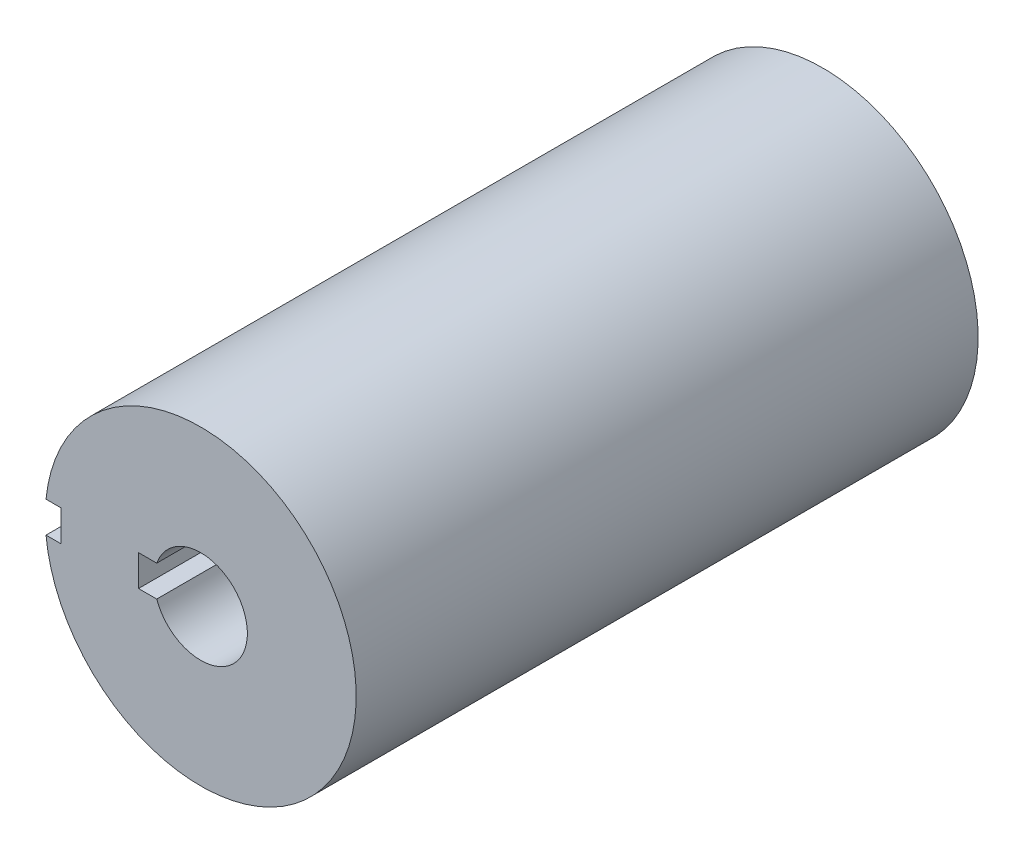
SolidWorks part; units mm, degrees
ref_plane "Front Plane" through (0, 0, 0) normal (0, 0, 1) x (1, 0, 0)
ref_plane "Top Plane" through (0, 0, 0) normal (0, 1, 0) x (1, 0, 0)
ref_plane "Right Plane" through (0, 0, 0) normal (1, 0, 0) x (0, 0, -1)
sketch "Sketch5" plane through (0, 0, 0) normal (0, 0, 1) x (1, 0, 0)
  circle A0 centre (0, 0) radius 5
  circle A1 centre (0, 0) radius 1.5
  dimension "D1" = 10
  dimension "D2" = 3
extrude "Boss-Extrude2" add sketch "Sketch5" along normal blind 12
sketch "Sketch6" plane through (0, 0, 12) normal (0, 0, 1) x (1, 0, 0)
  line L1 (-2, 0.5) -> (-1, 0.5)
  line L2 (-2, 0.5) -> (-2, -0.5)
  line L3 (-2, -0.5) -> (-1, -0.5)
  line L4 (-1, 0.5) -> (-1, -0.5)
  line L5 (-2, 0.5) -> (-1, -0.5) construction
  line L6 (-2, -0.5) -> (-1, 0.5) construction
  circle A0 centre (0, 0) radius 1.5 construction
  point P0 (-1.5, 0)
  dimension "D1" = 1
  dimension "D2" = 1
extrude "Cut-Extrude4" cut sketch "Sketch6" against normal blind 12
sketch "Sketch7" plane through (0, 0, 12) normal (0, 0, 1) x (1, 0, 0)
  line L1 (-5.5, 0.5) -> (-4.5, 0.5)
  line L2 (-5.5, 0.5) -> (-5.5, -0.5)
  line L3 (-5.5, -0.5) -> (-4.5, -0.5)
  line L4 (-4.5, 0.5) -> (-4.5, -0.5)
  line L5 (-5.5, 0.5) -> (-4.5, -0.5) construction
  line L6 (-5.5, -0.5) -> (-4.5, 0.5) construction
  circle A0 centre (0, 0) radius 5 construction
  point P0 (-5, 0)
  dimension "D1" = 1
  dimension "D2" = 1
extrude "Cut-Extrude6" cut sketch "Sketch7" against normal blind 4
sketch "Sketch8" plane through (0, 0, 0) normal (0, 0, -1) x (-1, 0, 0)
  line L1 (4.5, 0.5) -> (5.5, 0.5)
  line L2 (4.5, 0.5) -> (4.5, -0.5)
  line L3 (4.5, -0.5) -> (5.5, -0.5)
  line L4 (5.5, 0.5) -> (5.5, -0.5)
  line L5 (4.5, 0.5) -> (5.5, -0.5) construction
  line L6 (4.5, -0.5) -> (5.5, 0.5) construction
  circle A0 centre (0, 0) radius 5 construction
  point P0 (5, 0)
  dimension "D1" = 1
  dimension "D2" = 1
extrude "Cut-Extrude7" cut sketch "Sketch8" against normal blind 15
sketch "Sketch10" plane through (0, 0, 0) normal (0, 0, -1) x (-1, 0, 0)
  line L1 (5.5, 0.5) -> (4.5, 0.5)
  line L2 (5.5, 0.5) -> (5.5, -0.5)
  line L3 (5.5, -0.5) -> (4.5, -0.5)
  line L4 (4.5, 0.5) -> (4.5, -0.5)
  line L5 (5.5, 0.5) -> (4.5, -0.5) construction
  line L6 (5.5, -0.5) -> (4.5, 0.5) construction
  line L7 (1, 0.5) -> (2, 0.5)
  line L8 (1, 0.5) -> (1, -0.5)
  line L9 (1, -0.5) -> (2, -0.5)
  line L10 (2, 0.5) -> (2, -0.5)
  line L11 (1, 0.5) -> (2, -0.5) construction
  line L12 (1, -0.5) -> (2, 0.5) construction
  circle A0 centre (0, 0) radius 5
  circle A1 centre (0, 0) radius 1.5
  point P3 (5, 0)
  point P10 (1.5, 0)
  arc M1 (4.9749, 0.5) -> (4.9749, -0.5) centre (0, 0) ccw
  line M2 (4.9749, -0.5) -> (4.5, -0.5)
  line M3 (4.5, -0.5) -> (4.5, 0.5)
  line M4 (4.5, 0.5) -> (4.9749, 0.5)
  line M5 (2, 0.5) -> (2, -0.5)
  line M6 (2, -0.5) -> (1.4142, -0.5)
  arc M7 (1.4142, -0.5) -> (1.4142, 0.5) centre (0, 0) cw
  line M8 (1.4142, 0.5) -> (2, 0.5)
extrude "Boss-Extrude3" add sketch "Sketch10" along normal blind 8 contours M4 M1 M2 M3 M8 M5 M6 M7 region at (-4.7375, 0.6412, 0)
